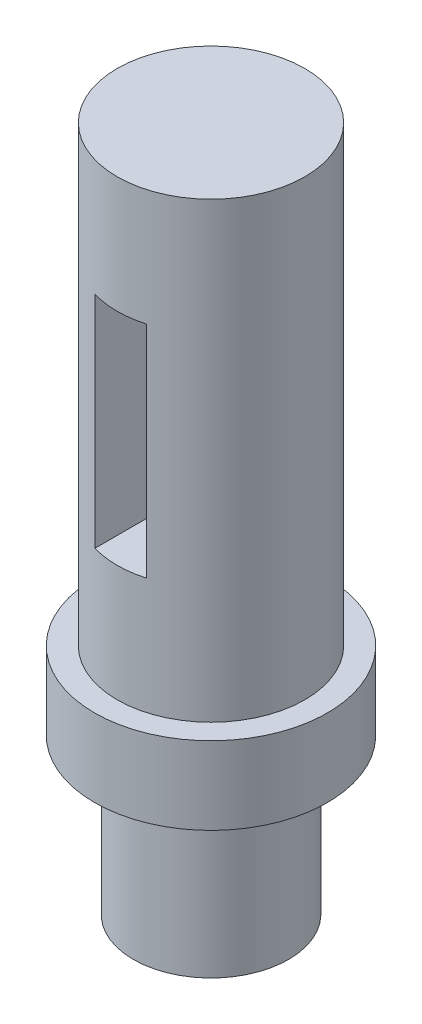
SolidWorks part; units mm, degrees
ref_plane "Front Plane" through (0, 0, 0) normal (0, 0, 1) x (1, 0, 0)
ref_plane "Top Plane" through (0, 0, 0) normal (0, 1, 0) x (1, 0, 0)
ref_plane "Right Plane" through (0, 0, 0) normal (1, 0, 0) x (0, 0, -1)
sketch "Sketch1" plane through (0, 0, 0) normal (0, 1, 0) x (1, 0, 0)
  circle A0 centre (0, 0) radius 18
  circle A1 centre (0, 0) radius 12
  circle A2 centre (0, 0) radius 14.5
  dimension "D1" = 36
  dimension "D2" = 24
  dimension "D3" = 29
extrude "Boss-Extrude1" add sketch "Sketch1" against normal blind 24 contours A1
extrude "Boss-Extrude2" add sketch "Sketch1<4>" along normal blind 12 contours A2 A1 | A1 | A0 A2 region at (-17.4909, 0, 0) region at (0, 0, 0) region at (-14.0899, 0, 0)
sketch "Sketch1<4>" plane through (0, 0, 0) normal (0, 1, 0) x (1, 0, 0) same geometry as "Sketch1"
extrude "Boss-Extrude4" add sketch "Sketch1<8>" along normal blind 70 from surface contours A2 starting at face at (0, 12, 18)
sketch "Sketch1<8>" plane through (0, 0, 0) normal (0, 1, 0) x (1, 0, 0) same geometry as "Sketch1"
sketch "Sketch2" plane through (0, 0, 0) normal (0, 0, 1) x (1, 0, 0)
  line L0 (0, 0) -> (0, 82) construction
  line L1 (-4, 64) -> (4, 64)
  line L2 (-4, 64) -> (-4, 30)
  line L3 (-4, 30) -> (4, 30)
  line L4 (4, 64) -> (4, 30)
  line L5 (-4, 64) -> (4, 30) construction
  line L6 (-4, 30) -> (4, 64) construction
  line L7 (14.5, 82) -> (-14.5, 82) construction
  point P0 (0, 47)
  point P10 (0, 64)
  dimension "D1" = 34
  dimension "D2" = 18
  dimension "D3" = 8
extrude "Cut-Extrude1" cut sketch "Sketch2" against normal through all both and the other way through all contours L2 L1 L4 L3
